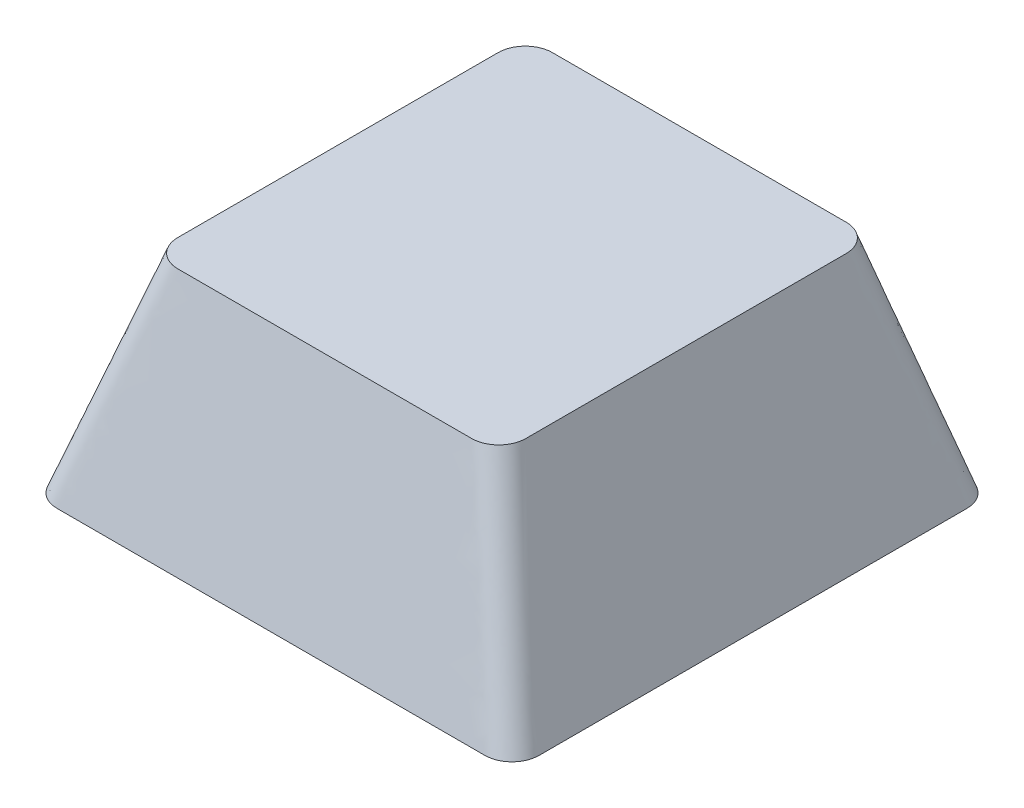
SolidWorks part; units mm, degrees
ref_plane "Alzado" through (0, 0, 0) normal (0, 0, 1) x (1, 0, 0)
ref_plane "Planta" through (0, 0, 0) normal (0, 1, 0) x (1, 0, 0)
ref_plane "Vista lateral" through (0, 0, 0) normal (1, 0, 0) x (0, 0, -1)
sketch "Croquis2" plane through (0, 0, 0) normal (0, 1, 0) x (1, 0, 0)
  line L1 (-7.9883, -9.0043) -> (7.9883, -9.0043)
  line L2 (-9.0043, -7.9883) -> (-9.0043, 7.9883)
  line L3 (-7.9883, 9.0043) -> (7.9883, 9.0043)
  line L4 (9.0043, -7.9883) -> (9.0043, 7.9883)
  arc A0 (-9.0043, 7.9883) -> (-7.9883, 9.0043) centre (-7.9883, 7.9883) cw
  arc A1 (-7.9883, -9.0043) -> (-9.0043, -7.9883) centre (-7.9883, -7.9883) cw
  arc A2 (7.9883, -9.0043) -> (9.0043, -7.9883) centre (7.9883, -7.9883) ccw
  arc A3 (7.9883, 9.0043) -> (9.0043, 7.9883) centre (7.9883, 7.9883) cw
  point P4 (9.0043, 0)
  point P6 (0, 9.0043)
  dimension "D3" = 1.016
  dimension "D1" = 18.0086
  dimension "D2" = 18.0086
ref_plane "Plano1" through (0, 8.001, 0) normal (0, 1, 0) x (1, 0, 0)
sketch "Croquis3" plane through (0, 8.001, 0) normal (0, 1, 0) x (1, 0, 0)
  line L1 (-5.4864, -6.9977) -> (5.4864, -6.9977)
  line L2 (-6.5024, -5.9817) -> (-6.5024, 5.9817)
  line L3 (-5.4864, 6.9977) -> (5.4864, 6.9977)
  line L4 (6.5024, -5.9817) -> (6.5024, 5.9817)
  line L5 (-6.5024, -6.9977) -> (6.5024, 6.9977) construction
  line L6 (-6.5024, 6.9977) -> (6.5024, -6.9977) construction
  arc A0 (5.4864, 6.9977) -> (6.5024, 5.9817) centre (5.4864, 5.9817) cw
  arc A1 (5.4864, -6.9977) -> (6.5024, -5.9817) centre (5.4864, -5.9817) ccw
  arc A2 (-5.4864, -6.9977) -> (-6.5024, -5.9817) centre (-5.4864, -5.9817) cw
  arc A3 (-6.5024, 5.9817) -> (-5.4864, 6.9977) centre (-5.4864, 5.9817) cw
  point P0 (0, 0)
  dimension "D3" = 1.016
  dimension "D1" = 13.0048
  dimension "D2" = 13.9954
loft "Recubrir1" add profiles "Croquis3", "Croquis2"
